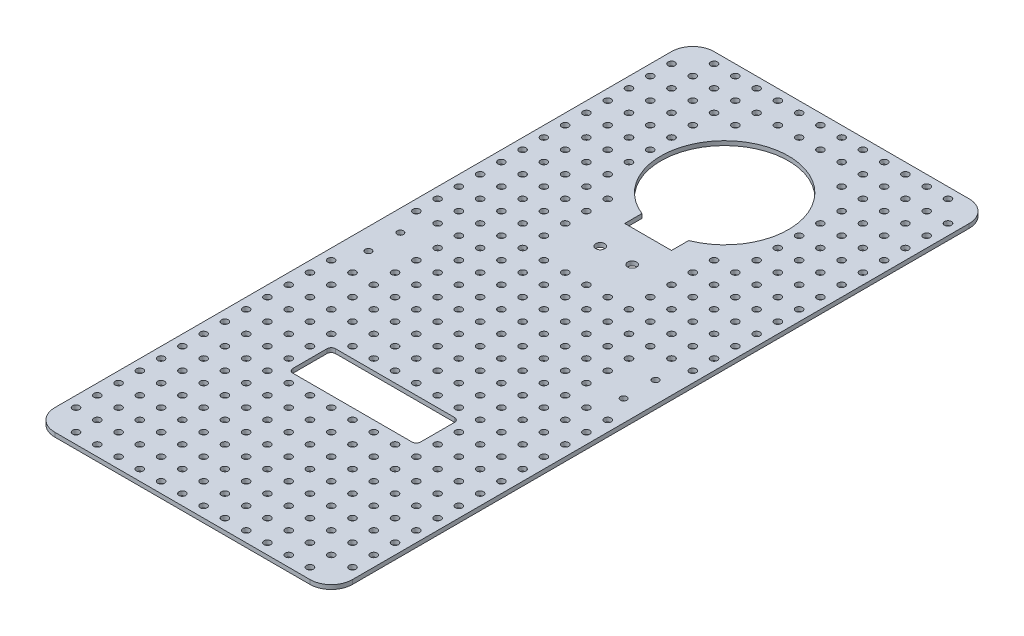
SolidWorks part; units mm, degrees
ref_plane "Спереди" through (0, 0, 0) normal (0, 0, 1) x (1, 0, 0)
ref_plane "Сверху" through (0, 0, 0) normal (0, 1, 0) x (1, 0, 0)
ref_plane "Справа" through (0, 0, 0) normal (1, 0, 0) x (0, 0, -1)
sketch "Эскиз1" plane through (0, 0, 0) normal (0, 1, 0) x (1, 0, 0)
  line L0 (0, 155) -> (0, -155) construction
  line L1 (-70, 155) -> (70, 155)
  line L2 (-70, 155) -> (-70, -155)
  line L3 (-70, -155) -> (70, -155)
  line L4 (70, 155) -> (70, -155)
  line L5 (-70, 0) -> (70, 0) construction
  dimension "D1" = 140
  dimension "D2" = 155
  dimension "D3" = 155
extrude "тело" add sketch "Эскиз1" along normal blind 2
sketch "Эскиз12" plane through (0, 2, 0) normal (0, 1, 0) x (1, 0, 0)
  line L0 (0, 155) -> (0, -155) construction
  line L1 (70, 155) -> (-70, 155) construction
  line L2 (-70, -155) -> (70, -155) construction
  line L3 (60, 7.5) -> (60, -7.5) construction
  line L4 (60, 0) -> (-60, 0) construction
  line L5 (-60, 7.5) -> (-60, -7.5) construction
  circle A0 centre (60, 7.5) radius 1.5
  circle A1 centre (-60, 7.5) radius 1.5
  circle A2 centre (-60, -7.5) radius 1.5
  circle A3 centre (60, -7.5) radius 1.5
  point P12 (-60, 0)
  point P17 (0, 0)
  point P19 (0, 0)
  dimension "D2" = 3
  dimension "D1" = 15
  dimension "D3" = 60
extrude "крепление подвески" cut sketch "Эскиз12" against normal through all
sketch "Эскиз5" plane through (0, 2, 0) normal (0, 1, 0) x (1, 0, 0)
  line L0 (-40, -150) -> (40, -80) construction
  line L1 (-40, -80) -> (40, -80) construction
  line L2 (-40, -80) -> (-40, -150) construction
  line L3 (-40, -150) -> (40, -150) construction
  line L4 (40, -80) -> (40, -150) construction
  line L5 (-40, -80) -> (40, -150) construction
  line L6 (-70, -155) -> (70, -155) construction
  circle A0 centre (-40, -80) radius 1.5
  circle A1 centre (40, -80) radius 1.5
  circle A2 centre (40, -150) radius 1.5
  circle A3 centre (-40, -150) radius 1.5
  point P12 (0, -115)
  dimension "D1" = 3
  dimension "D2" = 80
  dimension "D3" = 70
  dimension "D4" = 5
extrude "крепление raspberry" [suppressed] cut sketch "Эскиз5" against normal through all
sketch "Эскиз11" plane through (0, 2, 0) normal (0, 1, 0) x (1, 0, 0)
  line L0 (-30, -65) -> (30, -65) construction
  line L1 (-30, -55) -> (30, -55)
  line L2 (-30, -55) -> (-30, -75)
  line L3 (-30, -75) -> (30, -75)
  line L4 (30, -55) -> (30, -75)
  line L5 (-70, -155) -> (70, -155) construction
  point P11 (0, -55)
  dimension "D3" = 80
  dimension "D1" = 60
  dimension "D2" = 20
extrude "отверстие под провода на нижний этаж" cut sketch "Эскиз11" against normal through all
sketch "Эскиз9" [suppressed] plane through (0, 2, 0) normal (0, 1, 0) x (1, 0, 0)
  line L0 (0, -50) -> (0, 50) construction
  circle A0 centre (0, -98.5) radius 6.5
  circle A1 centre (0, -98.5) radius 15 construction
  circle A2 centre (0, -83.5) radius 1.5
  circle A3 centre (15, -98.5) radius 1.5
  circle A4 centre (-15, -98.5) radius 1.5
  circle A5 centre (0, -113.5) radius 1.5
  circle A6 centre (60, -18.5) radius 1.5 construction
  dimension "D2" = 13
  dimension "D3" = 30
  dimension "D4" = 3
  dimension "D1" = 80
extrude "ось вращения качалки" [suppressed] cut sketch "Эскиз9" against normal through all
fillet "Скругление3" radius 2 4 edges at (-30, 1, 75) (30, 1, 75) (30, 1, 55) (-30, 1, 55)
sketch "Эскиз15" plane through (0, 2, 0) normal (0, 1, 0) x (1, 0, 0)
  line L0 (-22.5, 148.75) -> (22.5, 148.75) construction
  line L1 (70, 155) -> (-70, 155) construction
  circle A0 centre (22.5, 148.75) radius 1.5
  circle A1 centre (-22.5, 148.75) radius 1.5
  point P6 (0, 148.75)
  dimension "D1" = 3
  dimension "D2" = 6.25
  dimension "D3" = 45
extrude "Крепление фронтальной камеры" [suppressed] cut sketch "Эскиз15" against normal up to next
sketch "Эскиз16" [suppressed] plane through (0, 2, 0) normal (0, 1, 0) x (1, 0, 0)
  line L0 (-56, -120) -> (-24, -120) construction
  line L1 (-68, -165) -> (68, -165) construction
  line L2 (-68, 143) -> (-68, -165) construction
  line L3 (0, -165) -> (0, 143) construction
  line L4 (68, 143) -> (-68, 143) construction
  circle A0 centre (-56, -120) radius 1.5
  circle A1 centre (-24, -120) radius 1.5
  circle A2 centre (24, -120) radius 1.5
  circle A3 centre (56, -120) radius 1.5
  dimension "D1" = 32
  dimension "D4" = 3
  dimension "D2" = 45
  dimension "D3" = 12
extrude "Крепление силовых уголков со стороны буллета" [suppressed] cut sketch "Эскиз16" against normal up to next
sketch "Эскиз17" [suppressed] plane through (0, 2, 0) normal (0, 1, 0) x (1, 0, 0)
  line L1 (48, -110) -> (53, -110)
  line L2 (48, -110) -> (48, -123)
  line L3 (48, -123) -> (53, -123)
  line L4 (53, -110) -> (53, -123)
  circle A0 centre (40, -90) radius 1.5 construction
  dimension "D4" = 20
  dimension "D1" = 8
  dimension "D2" = 13
  dimension "D3" = 5
extrude "Отверстие по дпитание сервоприводов и шилда" [suppressed] cut sketch "Эскиз17" against normal up to next
sketch "Эскиз18" plane through (0, 2, 0) normal (0, 1, 0) x (1, 0, 0)
  line L0 (0, 0) -> (0, 155) construction
  line L1 (70, 155) -> (-70, 155) construction
  line L6 (-11, 64) -> (11, 64)
  line L7 (11, 64) -> (11, 72.0894)
  line L8 (-11, 72.0894) -> (-11, 64)
  line L12 (7.5, 49) -> (-7.5, 49) construction
  line L23 (70, 155) -> (-70, 155) construction
  circle A3 centre (7.5, 49) radius 2.1
  circle A10 centre (-7.5, 49) radius 2.1
  arc A11 (11, 72.0894) -> (-11, 72.0894) centre (0, 100) ccw
  point P7 (0, 64)
  point P15 (0, 49)
  dimension "D6" = 60
  dimension "D2" = 4.2
  dimension "D1" = 22
  dimension "D3" = 15
  dimension "D4" = 15
  dimension "D5" = 36
  dimension "D7" = 55
fillet "Скругление6" [suppressed] radius 2
extrude "Вырез под манипулятор" cut sketch "Эскиз18" against normal through all
fillet "Скругление9" radius 10 4 edges at (-70, 1, 155) (70, 1, 155) (70, 1, -155) (-70, 1, -155)
sketch "Эскиз19" plane through (0, 2, 0) normal (0, 1, 0) x (1, 0, 0)
  line L0 (-17.5, -150) -> (17.5, -150) construction
  line L1 (-60, -155) -> (60, -155) construction
  circle A0 centre (-17.5, -150) radius 1.5
  circle A1 centre (17.5, -150) radius 1.5
  point P6 (0, -150)
  point P7 (0, -155)
  dimension "D1" = 3
  dimension "D2" = 35
  dimension "D3" = 5
extrude "Крепление разъема ХТ60Е_М" [suppressed] cut sketch "Эскиз19" against normal through all
sketch "Эскиз20" plane through (0, 0, 0) normal (0, -1, 0) x (1, 0, 0)
  line L0 (0, 155) -> (0, -155) construction
  line L1 (-60, 155) -> (60, 155) construction
  line L2 (60, -155) -> (-60, -155) construction
  circle A0 centre (-5, 150) radius 1.6
  circle A1 centre (5, 150) radius 1.6
  circle A2 centre (15, 150) radius 1.6
  circle A3 centre (25, 150) radius 1.6
  circle A4 centre (35, 150) radius 1.6
  circle A5 centre (45, 150) radius 1.6
  circle A6 centre (55, 150) radius 1.6
  circle A8 centre (65, 150) radius 1.6 [skipped]
  circle A9 centre (-15, 150) radius 1.6
  circle A10 centre (-25, 150) radius 1.6
  circle A11 centre (-35, 150) radius 1.6
  circle A12 centre (-45, 150) radius 1.6
  circle A13 centre (-55, 150) radius 1.6
  circle A14 centre (-5, 140) radius 1.6
  circle A15 centre (5, 140) radius 1.6
  circle A16 centre (15, 140) radius 1.6
  circle A17 centre (25, 140) radius 1.6
  circle A18 centre (35, 140) radius 1.6
  circle A19 centre (45, 140) radius 1.6
  circle A20 centre (55, 140) radius 1.6
  circle A21 centre (-15, 140) radius 1.6
  circle A22 centre (-25, 140) radius 1.6
  circle A23 centre (-35, 140) radius 1.6
  circle A24 centre (-45, 140) radius 1.6
  circle A25 centre (-55, 140) radius 1.6
  circle A26 centre (-5, 130) radius 1.6
  circle A27 centre (5, 130) radius 1.6
  circle A28 centre (15, 130) radius 1.6
  circle A29 centre (25, 130) radius 1.6
  circle A30 centre (35, 130) radius 1.6
  circle A31 centre (45, 130) radius 1.6
  circle A32 centre (55, 130) radius 1.6
  circle A33 centre (-15, 130) radius 1.6
  circle A34 centre (-25, 130) radius 1.6
  circle A35 centre (-35, 130) radius 1.6
  circle A36 centre (-45, 130) radius 1.6
  circle A37 centre (-55, 130) radius 1.6
  circle A38 centre (-5, 120) radius 1.6
  circle A39 centre (5, 120) radius 1.6
  circle A40 centre (15, 120) radius 1.6
  circle A41 centre (25, 120) radius 1.6
  circle A42 centre (35, 120) radius 1.6
  circle A43 centre (45, 120) radius 1.6
  circle A44 centre (55, 120) radius 1.6
  circle A45 centre (-15, 120) radius 1.6
  circle A46 centre (-25, 120) radius 1.6
  circle A47 centre (-35, 120) radius 1.6
  circle A48 centre (-45, 120) radius 1.6
  circle A49 centre (-55, 120) radius 1.6
  circle A50 centre (-5, 110) radius 1.6
  circle A51 centre (5, 110) radius 1.6
  circle A52 centre (15, 110) radius 1.6
  circle A53 centre (25, 110) radius 1.6
  circle A54 centre (35, 110) radius 1.6
  circle A55 centre (45, 110) radius 1.6
  circle A56 centre (55, 110) radius 1.6
  circle A57 centre (-15, 110) radius 1.6
  circle A58 centre (-25, 110) radius 1.6
  circle A59 centre (-35, 110) radius 1.6
  circle A60 centre (-45, 110) radius 1.6
  circle A61 centre (-55, 110) radius 1.6
  circle A62 centre (-5, 100) radius 1.6
  circle A63 centre (5, 100) radius 1.6
  circle A64 centre (15, 100) radius 1.6
  circle A65 centre (25, 100) radius 1.6
  circle A66 centre (35, 100) radius 1.6
  circle A67 centre (45, 100) radius 1.6
  circle A68 centre (55, 100) radius 1.6
  circle A69 centre (-15, 100) radius 1.6
  circle A70 centre (-25, 100) radius 1.6
  circle A71 centre (-35, 100) radius 1.6
  circle A72 centre (-45, 100) radius 1.6
  circle A73 centre (-55, 100) radius 1.6
  circle A74 centre (-5, 90) radius 1.6
  circle A75 centre (5, 90) radius 1.6
  circle A76 centre (15, 90) radius 1.6
  circle A77 centre (25, 90) radius 1.6
  circle A78 centre (35, 90) radius 1.6
  circle A79 centre (45, 90) radius 1.6
  circle A80 centre (55, 90) radius 1.6
  circle A81 centre (-15, 90) radius 1.6
  circle A82 centre (-25, 90) radius 1.6
  circle A83 centre (-35, 90) radius 1.6
  circle A84 centre (-45, 90) radius 1.6
  circle A85 centre (-55, 90) radius 1.6
  circle A86 centre (-5, 80) radius 1.6
  circle A87 centre (5, 80) radius 1.6
  circle A88 centre (15, 80) radius 1.6
  circle A89 centre (25, 80) radius 1.6
  circle A90 centre (35, 80) radius 1.6
  circle A91 centre (45, 80) radius 1.6
  circle A92 centre (55, 80) radius 1.6
  circle A93 centre (-15, 80) radius 1.6
  circle A94 centre (-25, 80) radius 1.6
  circle A95 centre (-35, 80) radius 1.6
  circle A96 centre (-45, 80) radius 1.6
  circle A97 centre (-55, 80) radius 1.6
  circle A98 centre (-5, 70) radius 1.6 construction
  circle A99 centre (5, 70) radius 1.6 construction
  circle A100 centre (15, 70) radius 1.6 construction
  circle A101 centre (25, 70) radius 1.6 construction
  circle A102 centre (35, 70) radius 1.6
  circle A103 centre (45, 70) radius 1.6
  circle A104 centre (55, 70) radius 1.6
  circle A105 centre (-15, 70) radius 1.6 construction
  circle A106 centre (-25, 70) radius 1.6 construction
  circle A107 centre (-35, 70) radius 1.6
  circle A108 centre (-45, 70) radius 1.6
  circle A109 centre (-55, 70) radius 1.6
  circle A110 centre (-5, 60) radius 1.6 construction
  circle A111 centre (5, 60) radius 1.6 construction
  circle A112 centre (15, 60) radius 1.6 construction
  circle A113 centre (25, 60) radius 1.6 construction
  circle A114 centre (35, 60) radius 1.6
  circle A115 centre (45, 60) radius 1.6
  circle A116 centre (55, 60) radius 1.6
  circle A117 centre (-15, 60) radius 1.6 construction
  circle A118 centre (-25, 60) radius 1.6 construction
  circle A119 centre (-35, 60) radius 1.6
  circle A120 centre (-45, 60) radius 1.6
  circle A121 centre (-55, 60) radius 1.6
  circle A122 centre (-5, 50) radius 1.6
  circle A123 centre (5, 50) radius 1.6
  circle A124 centre (15, 50) radius 1.6
  circle A125 centre (25, 50) radius 1.6
  circle A126 centre (35, 50) radius 1.6
  circle A127 centre (45, 50) radius 1.6
  circle A128 centre (55, 50) radius 1.6
  circle A129 centre (-15, 50) radius 1.6
  circle A130 centre (-25, 50) radius 1.6
  circle A131 centre (-35, 50) radius 1.6
  circle A132 centre (-45, 50) radius 1.6
  circle A133 centre (-55, 50) radius 1.6
  circle A134 centre (-5, 40) radius 1.6
  circle A135 centre (5, 40) radius 1.6
  circle A136 centre (15, 40) radius 1.6
  circle A137 centre (25, 40) radius 1.6
  circle A138 centre (35, 40) radius 1.6
  circle A139 centre (45, 40) radius 1.6
  circle A140 centre (55, 40) radius 1.6
  circle A141 centre (-15, 40) radius 1.6
  circle A142 centre (-25, 40) radius 1.6
  circle A143 centre (-35, 40) radius 1.6
  circle A144 centre (-45, 40) radius 1.6
  circle A145 centre (-55, 40) radius 1.6
  circle A146 centre (-5, 30) radius 1.6
  circle A147 centre (5, 30) radius 1.6
  circle A148 centre (15, 30) radius 1.6
  circle A149 centre (25, 30) radius 1.6
  circle A150 centre (35, 30) radius 1.6
  circle A151 centre (45, 30) radius 1.6
  circle A152 centre (55, 30) radius 1.6
  circle A153 centre (-15, 30) radius 1.6
  circle A154 centre (-25, 30) radius 1.6
  circle A155 centre (-35, 30) radius 1.6
  circle A156 centre (-45, 30) radius 1.6
  circle A157 centre (-55, 30) radius 1.6
  circle A158 centre (-5, 20) radius 1.6
  circle A159 centre (5, 20) radius 1.6
  circle A160 centre (15, 20) radius 1.6
  circle A161 centre (25, 20) radius 1.6
  circle A162 centre (35, 20) radius 1.6
  circle A163 centre (45, 20) radius 1.6
  circle A164 centre (55, 20) radius 1.6
  circle A165 centre (-15, 20) radius 1.6
  circle A166 centre (-25, 20) radius 1.6
  circle A167 centre (-35, 20) radius 1.6
  circle A168 centre (-45, 20) radius 1.6
  circle A169 centre (-55, 20) radius 1.6
  circle A170 centre (-5, 10) radius 1.6
  circle A171 centre (5, 10) radius 1.6
  circle A172 centre (15, 10) radius 1.6
  circle A173 centre (25, 10) radius 1.6
  circle A174 centre (35, 10) radius 1.6
  circle A175 centre (45, 10) radius 1.6
  circle A176 centre (55, 10) radius 1.6 construction
  circle A177 centre (-15, 10) radius 1.6
  circle A178 centre (-25, 10) radius 1.6
  circle A179 centre (-35, 10) radius 1.6
  circle A180 centre (-45, 10) radius 1.6
  circle A181 centre (-55, 10) radius 1.6 construction
  circle A182 centre (-5, 0) radius 1.6
  circle A183 centre (5, 0) radius 1.6
  circle A184 centre (15, 0) radius 1.6
  circle A185 centre (25, 0) radius 1.6
  circle A186 centre (35, 0) radius 1.6
  circle A187 centre (45, 0) radius 1.6
  circle A188 centre (55, 0) radius 1.6 construction
  circle A189 centre (-15, 0) radius 1.6
  circle A190 centre (-25, 0) radius 1.6
  circle A191 centre (-35, 0) radius 1.6
  circle A192 centre (-45, 0) radius 1.6
  circle A193 centre (-55, 0) radius 1.6 construction
  circle A194 centre (-5, -10) radius 1.6
  circle A195 centre (5, -10) radius 1.6
  circle A196 centre (15, -10) radius 1.6
  circle A197 centre (25, -10) radius 1.6
  circle A198 centre (35, -10) radius 1.6
  circle A199 centre (45, -10) radius 1.6
  circle A200 centre (55, -10) radius 1.6 construction
  circle A201 centre (-15, -10) radius 1.6
  circle A202 centre (-25, -10) radius 1.6
  circle A203 centre (-35, -10) radius 1.6
  circle A204 centre (-45, -10) radius 1.6
  circle A205 centre (-55, -10) radius 1.6 construction
  circle A206 centre (-5, -20) radius 1.6
  circle A207 centre (5, -20) radius 1.6
  circle A208 centre (15, -20) radius 1.6
  circle A209 centre (25, -20) radius 1.6
  circle A210 centre (35, -20) radius 1.6
  circle A211 centre (45, -20) radius 1.6
  circle A212 centre (55, -20) radius 1.6
  circle A213 centre (-15, -20) radius 1.6
  circle A214 centre (-25, -20) radius 1.6
  circle A215 centre (-35, -20) radius 1.6
  circle A216 centre (-45, -20) radius 1.6
  circle A217 centre (-55, -20) radius 1.6
  circle A218 centre (-5, -30) radius 1.6
  circle A219 centre (5, -30) radius 1.6
  circle A220 centre (15, -30) radius 1.6
  circle A221 centre (25, -30) radius 1.6
  circle A222 centre (35, -30) radius 1.6
  circle A223 centre (45, -30) radius 1.6
  circle A224 centre (55, -30) radius 1.6
  circle A225 centre (-15, -30) radius 1.6
  circle A226 centre (-25, -30) radius 1.6
  circle A227 centre (-35, -30) radius 1.6
  circle A228 centre (-45, -30) radius 1.6
  circle A229 centre (-55, -30) radius 1.6
  circle A230 centre (-5, -40) radius 1.6 construction
  circle A231 centre (5, -40) radius 1.6 construction
  circle A232 centre (15, -40) radius 1.6 construction
  circle A233 centre (25, -40) radius 1.6
  circle A234 centre (35, -40) radius 1.6
  circle A235 centre (45, -40) radius 1.6
  circle A236 centre (55, -40) radius 1.6
  circle A237 centre (-15, -40) radius 1.6 construction
  circle A238 centre (-25, -40) radius 1.6
  circle A239 centre (-35, -40) radius 1.6
  circle A240 centre (-45, -40) radius 1.6
  circle A241 centre (-55, -40) radius 1.6
  circle A242 centre (-5, -50) radius 1.6 construction
  circle A243 centre (5, -50) radius 1.6 construction
  circle A244 centre (15, -50) radius 1.6 construction
  circle A245 centre (25, -50) radius 1.6
  circle A246 centre (35, -50) radius 1.6
  circle A247 centre (45, -50) radius 1.6
  circle A248 centre (55, -50) radius 1.6
  circle A249 centre (-15, -50) radius 1.6 construction
  circle A250 centre (-25, -50) radius 1.6
  circle A251 centre (-35, -50) radius 1.6
  circle A252 centre (-45, -50) radius 1.6
  circle A253 centre (-55, -50) radius 1.6
  circle A254 centre (-5, -60) radius 1.6 construction
  circle A255 centre (5, -60) radius 1.6 construction
  circle A256 centre (15, -60) radius 1.6 construction
  circle A257 centre (25, -60) radius 1.6
  circle A258 centre (35, -60) radius 1.6
  circle A259 centre (45, -60) radius 1.6
  circle A260 centre (55, -60) radius 1.6
  circle A261 centre (-15, -60) radius 1.6 construction
  circle A262 centre (-25, -60) radius 1.6
  circle A263 centre (-35, -60) radius 1.6
  circle A264 centre (-45, -60) radius 1.6
  circle A265 centre (-55, -60) radius 1.6
  circle A266 centre (-5, -70) radius 1.6 construction
  circle A267 centre (5, -70) radius 1.6 construction
  circle A268 centre (15, -70) radius 1.6 construction
  circle A269 centre (25, -70) radius 1.6
  circle A270 centre (35, -70) radius 1.6
  circle A271 centre (45, -70) radius 1.6
  circle A272 centre (55, -70) radius 1.6
  circle A273 centre (-15, -70) radius 1.6 construction
  circle A274 centre (-25, -70) radius 1.6
  circle A275 centre (-35, -70) radius 1.6
  circle A276 centre (-45, -70) radius 1.6
  circle A277 centre (-55, -70) radius 1.6
  circle A278 centre (-5, -80) radius 1.6 construction
  circle A279 centre (5, -80) radius 1.6 construction
  circle A280 centre (15, -80) radius 1.6 construction
  circle A281 centre (25, -80) radius 1.6 construction
  circle A282 centre (35, -80) radius 1.6
  circle A283 centre (45, -80) radius 1.6
  circle A284 centre (55, -80) radius 1.6
  circle A285 centre (-15, -80) radius 1.6 construction
  circle A286 centre (-25, -80) radius 1.6 construction
  circle A287 centre (-35, -80) radius 1.6
  circle A288 centre (-45, -80) radius 1.6
  circle A289 centre (-55, -80) radius 1.6
  circle A290 centre (-5, -90) radius 1.6 construction
  circle A291 centre (5, -90) radius 1.6 construction
  circle A292 centre (15, -90) radius 1.6 construction
  circle A293 centre (25, -90) radius 1.6 construction
  circle A294 centre (35, -90) radius 1.6
  circle A295 centre (45, -90) radius 1.6
  circle A296 centre (55, -90) radius 1.6
  circle A297 centre (-15, -90) radius 1.6 construction
  circle A298 centre (-25, -90) radius 1.6 construction
  circle A299 centre (-35, -90) radius 1.6
  circle A300 centre (-45, -90) radius 1.6
  circle A301 centre (-55, -90) radius 1.6
  circle A302 centre (-5, -100) radius 1.6 construction
  circle A303 centre (5, -100) radius 1.6 construction
  circle A304 centre (15, -100) radius 1.6 construction
  circle A305 centre (25, -100) radius 1.6 construction
  circle A306 centre (35, -100) radius 1.6
  circle A307 centre (45, -100) radius 1.6
  circle A308 centre (55, -100) radius 1.6
  circle A309 centre (-15, -100) radius 1.6 construction
  circle A310 centre (-25, -100) radius 1.6 construction
  circle A311 centre (-35, -100) radius 1.6
  circle A312 centre (-45, -100) radius 1.6
  circle A313 centre (-55, -100) radius 1.6
  circle A314 centre (-5, -110) radius 1.6 construction
  circle A315 centre (5, -110) radius 1.6 construction
  circle A316 centre (15, -110) radius 1.6 construction
  circle A317 centre (25, -110) radius 1.6 construction
  circle A318 centre (35, -110) radius 1.6
  circle A319 centre (45, -110) radius 1.6
  circle A320 centre (55, -110) radius 1.6
  circle A321 centre (-15, -110) radius 1.6 construction
  circle A322 centre (-25, -110) radius 1.6 construction
  circle A323 centre (-35, -110) radius 1.6
  circle A324 centre (-45, -110) radius 1.6
  circle A325 centre (-55, -110) radius 1.6
  circle A326 centre (-5, -120) radius 1.6 construction
  circle A327 centre (5, -120) radius 1.6 construction
  circle A328 centre (15, -120) radius 1.6 construction
  circle A329 centre (25, -120) radius 1.6 construction
  circle A330 centre (35, -120) radius 1.6
  circle A331 centre (45, -120) radius 1.6
  circle A332 centre (55, -120) radius 1.6
  circle A333 centre (-15, -120) radius 1.6 construction
  circle A334 centre (-25, -120) radius 1.6 construction
  circle A335 centre (-35, -120) radius 1.6
  circle A336 centre (-45, -120) radius 1.6
  circle A337 centre (-55, -120) radius 1.6
  circle A338 centre (-5, -130) radius 1.6 construction
  circle A339 centre (5, -130) radius 1.6 construction
  circle A340 centre (15, -130) radius 1.6 construction
  circle A341 centre (25, -130) radius 1.6
  circle A342 centre (35, -130) radius 1.6
  circle A343 centre (45, -130) radius 1.6
  circle A344 centre (55, -130) radius 1.6
  circle A345 centre (-15, -130) radius 1.6 construction
  circle A346 centre (-25, -130) radius 1.6
  circle A347 centre (-35, -130) radius 1.6
  circle A348 centre (-45, -130) radius 1.6
  circle A349 centre (-55, -130) radius 1.6
  circle A350 centre (-5, -140) radius 1.6
  circle A351 centre (5, -140) radius 1.6
  circle A352 centre (15, -140) radius 1.6
  circle A353 centre (25, -140) radius 1.6
  circle A354 centre (35, -140) radius 1.6
  circle A355 centre (45, -140) radius 1.6
  circle A356 centre (55, -140) radius 1.6
  circle A357 centre (-15, -140) radius 1.6
  circle A358 centre (-25, -140) radius 1.6
  circle A359 centre (-35, -140) radius 1.6
  circle A360 centre (-45, -140) radius 1.6
  circle A361 centre (-55, -140) radius 1.6
  circle A362 centre (-5, -150) radius 1.6
  circle A363 centre (5, -150) radius 1.6
  circle A364 centre (15, -150) radius 1.6
  circle A365 centre (25, -150) radius 1.6
  circle A366 centre (35, -150) radius 1.6
  circle A367 centre (45, -150) radius 1.6
  circle A368 centre (55, -150) radius 1.6
  circle A369 centre (-15, -150) radius 1.6
  circle A370 centre (-25, -150) radius 1.6
  circle A371 centre (-35, -150) radius 1.6
  circle A372 centre (-45, -150) radius 1.6
  circle A373 centre (-55, -150) radius 1.6
  circle A374 centre (-65, 150) radius 1.6 construction
  circle A375 centre (-65, 140) radius 1.6
  circle A376 centre (-65, 130) radius 1.6
  circle A377 centre (-65, 120) radius 1.6
  circle A378 centre (-65, 110) radius 1.6
  circle A379 centre (-65, 100) radius 1.6
  circle A380 centre (-65, 90) radius 1.6
  circle A381 centre (-65, 80) radius 1.6
  circle A382 centre (-65, 70) radius 1.6
  circle A383 centre (-65, 60) radius 1.6
  circle A384 centre (-65, 50) radius 1.6
  circle A385 centre (-65, 40) radius 1.6
  circle A386 centre (-65, 30) radius 1.6
  circle A387 centre (-65, 20) radius 1.6
  circle A388 centre (-65, 10) radius 1.6 construction
  circle A389 centre (-65, 0) radius 1.6 construction
  circle A390 centre (-65, -10) radius 1.6 construction
  circle A391 centre (-65, -20) radius 1.6
  circle A392 centre (-65, -30) radius 1.6
  circle A393 centre (-65, -40) radius 1.6
  circle A394 centre (-65, -50) radius 1.6
  circle A395 centre (-65, -60) radius 1.6
  circle A396 centre (-65, -70) radius 1.6
  circle A397 centre (-65, -80) radius 1.6
  circle A398 centre (-65, -90) radius 1.6
  circle A399 centre (-65, -100) radius 1.6
  circle A400 centre (-65, -110) radius 1.6
  circle A401 centre (-65, -120) radius 1.6
  circle A402 centre (-65, -130) radius 1.6
  circle A403 centre (-65, -140) radius 1.6
  circle A404 centre (-65, -150) radius 1.6 construction
  circle A405 centre (65, 150) radius 1.6 construction
  circle A406 centre (65, 140) radius 1.6
  circle A407 centre (65, 130) radius 1.6
  circle A408 centre (65, 120) radius 1.6
  circle A409 centre (65, 110) radius 1.6
  circle A410 centre (65, 100) radius 1.6
  circle A411 centre (65, 90) radius 1.6
  circle A412 centre (65, 80) radius 1.6
  circle A413 centre (65, 70) radius 1.6
  circle A414 centre (65, 60) radius 1.6
  circle A415 centre (65, 50) radius 1.6
  circle A416 centre (65, 40) radius 1.6
  circle A417 centre (65, 30) radius 1.6
  circle A418 centre (65, 20) radius 1.6
  circle A419 centre (65, 10) radius 1.6 construction
  circle A420 centre (65, 0) radius 1.6 construction
  circle A421 centre (65, -10) radius 1.6 construction
  circle A422 centre (65, -20) radius 1.6
  circle A423 centre (65, -30) radius 1.6
  circle A424 centre (65, -40) radius 1.6
  circle A425 centre (65, -50) radius 1.6
  circle A426 centre (65, -60) radius 1.6
  circle A427 centre (65, -70) radius 1.6
  circle A428 centre (65, -80) radius 1.6
  circle A429 centre (65, -90) radius 1.6
  circle A430 centre (65, -100) radius 1.6
  circle A431 centre (65, -110) radius 1.6
  circle A432 centre (65, -120) radius 1.6
  circle A433 centre (65, -130) radius 1.6
  circle A434 centre (65, -140) radius 1.6
  circle A435 centre (65, -150) radius 1.6 construction
  dimension "D1" = 3.2
  dimension "D9" = 10
  dimension "D2" = 5
  dimension "D3" = 5
  dimension "D5" = 6
  dimension "D7" = 2
  dimension "D10" = 10
  dimension "D11" = 10
  dimension "D12" = 10
  dimension "D13" = 10
  dimension "D4" = 8
  dimension "D6" = 31
  dimension "D8" = 2
extrude "Сетка 10мм" cut sketch "Эскиз20" against normal up to next (2 mm away)
